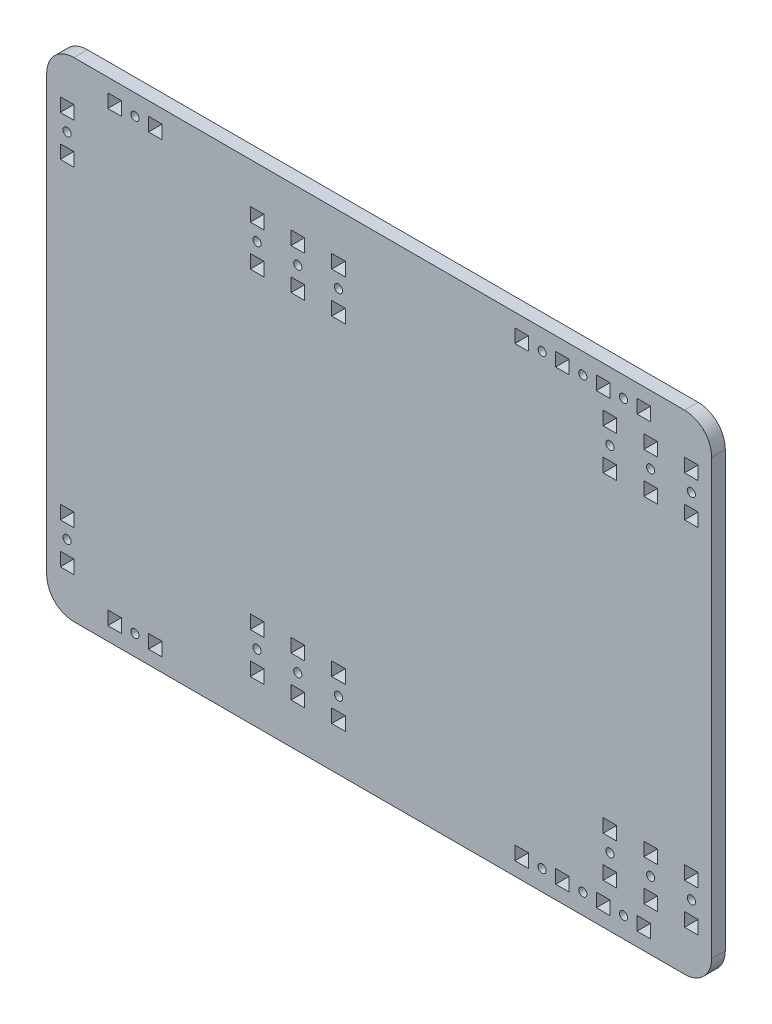
SolidWorks part; units mm, degrees
ref_plane "Front Plane" through (0, 0, 0) normal (0, 0, 1) x (1, 0, 0)
ref_plane "Top Plane" through (0, 0, 0) normal (0, 1, 0) x (1, 0, 0)
ref_plane "Right Plane" through (0, 0, 0) normal (1, 0, 0) x (0, 0, -1)
sketch "Sketch1" plane through (0, 0, 0) normal (0, 0, 1) x (1, 0, 0)
  line L0 (0, 0) -> (264.3375, 0) construction
  line L1 (-91.3244, 90) -> (153.676, 90)
  line L5 (23.6756, 97.7888) -> (23.6756, -107.1048) construction
  line L6 (-92.4996, 82.5) -> (92.5, 82.5) construction
  line L7 (92.5, -82.5) -> (-92.4996, -82.5) construction
  line L8 (-91.3244, 90) -> (-91.3244, -90)
  line L51 (-83.8244, 77.0051) -> (-83.8244, -67.4641) construction
  line L105 (-91.3244, -90) -> (153.676, -90)
  line L122 (153.676, 90) -> (153.676, -90)
  line L124 (-83.8244, 65) -> (153.676, 65) construction
  line L125 (-83.8244, -65) -> (153.676, -65) construction
  point P1 (0, 0)
  point P7 (13.7314, -65)
  point P12 (1.3999, -57.5347)
  point P13 (0, -65)
  point P14 (-14.2347, -65)
  point P26 (127.5, -49.75)
  line B0 (-63.8248, 82.5) -> (-53.8248, 82.5) construction
  line B1 (-63.8248, 85) -> (-68.8248, 85)
  line B2 (-63.8248, 85) -> (-63.8248, 80)
  line B3 (-63.8248, 80) -> (-68.8248, 80)
  line B4 (-68.8248, 85) -> (-68.8248, 80)
  line B5 (-53.8248, 85) -> (-48.8248, 85)
  line B6 (-53.8248, 85) -> (-53.8248, 80)
  line B7 (-53.8248, 80) -> (-48.8248, 80)
  line B8 (-48.8248, 85) -> (-48.8248, 80)
  line B9 (-58.8248, 82.5) -> (-58.8248, 89.4724) construction
  circle B10 centre (-58.8248, 82.5) radius 1.5
  line B11 (111.176, 82.5) -> (101.176, 82.5) construction
  line B12 (111.176, 85) -> (116.176, 85)
  line B13 (111.176, 85) -> (111.176, 80)
  line B14 (111.176, 80) -> (116.176, 80)
  line B15 (116.176, 85) -> (116.176, 80)
  line B16 (101.176, 85) -> (96.176, 85)
  line B17 (101.176, 85) -> (101.176, 80)
  line B18 (101.176, 80) -> (96.176, 80)
  line B19 (96.176, 85) -> (96.176, 80)
  line B20 (106.176, 82.5) -> (106.176, 89.4724) construction
  circle B21 centre (106.176, 82.5) radius 1.5
  line B22 (111.176, -82.5) -> (101.176, -82.5) construction
  line B23 (111.176, -85) -> (116.176, -85)
  line B24 (111.176, -85) -> (111.176, -80)
  line B25 (111.176, -80) -> (116.176, -80)
  line B26 (116.176, -85) -> (116.176, -80)
  line B27 (101.176, -85) -> (96.176, -85)
  line B28 (101.176, -85) -> (101.176, -80)
  line B29 (101.176, -80) -> (96.176, -80)
  line B30 (96.176, -85) -> (96.176, -80)
  line B31 (106.176, -82.5) -> (106.176, -89.4724) construction
  circle B32 centre (106.176, -82.5) radius 1.5
  line B33 (-63.8248, -82.5) -> (-53.8248, -82.5) construction
  line B34 (-63.8248, -85) -> (-68.8248, -85)
  line B35 (-63.8248, -85) -> (-63.8248, -80)
  line B36 (-63.8248, -80) -> (-68.8248, -80)
  line B37 (-68.8248, -85) -> (-68.8248, -80)
  line B38 (-53.8248, -85) -> (-48.8248, -85)
  line B39 (-53.8248, -85) -> (-53.8248, -80)
  line B40 (-53.8248, -80) -> (-48.8248, -80)
  line B41 (-48.8248, -85) -> (-48.8248, -80)
  line B42 (-58.8248, -82.5) -> (-58.8248, -89.4724) construction
  circle B43 centre (-58.8248, -82.5) radius 1.5
  line B44 (96.176, 82.5) -> (86.176, 82.5) construction
  line B45 (96.176, 85) -> (101.176, 85)
  line B46 (96.176, 85) -> (96.176, 80)
  line B47 (96.176, 80) -> (101.176, 80)
  line B48 (101.176, 85) -> (101.176, 80)
  line B49 (86.176, 85) -> (81.176, 85)
  line B50 (86.176, 85) -> (86.176, 80)
  line B51 (86.176, 80) -> (81.176, 80)
  line B52 (81.176, 85) -> (81.176, 80)
  line B53 (91.176, 82.5) -> (91.176, 89.4724) construction
  circle B54 centre (91.176, 82.5) radius 1.5
  line B55 (126.176, 82.5) -> (116.176, 82.5) construction
  line B56 (126.176, 85) -> (131.176, 85)
  line B57 (126.176, 85) -> (126.176, 80)
  line B58 (126.176, 80) -> (131.176, 80)
  line B59 (131.176, 85) -> (131.176, 80)
  line B60 (116.176, 85) -> (111.176, 85)
  line B61 (116.176, 85) -> (116.176, 80)
  line B62 (116.176, 80) -> (111.176, 80)
  line B63 (111.176, 85) -> (111.176, 80)
  line B64 (121.176, 82.5) -> (121.176, 89.4724) construction
  circle B65 centre (121.176, 82.5) radius 1.5
  line B66 (96.176, -82.5) -> (86.176, -82.5) construction
  line B67 (96.176, -85) -> (101.176, -85)
  line B68 (96.176, -85) -> (96.176, -80)
  line B69 (96.176, -80) -> (101.176, -80)
  line B70 (101.176, -85) -> (101.176, -80)
  line B71 (86.176, -85) -> (81.176, -85)
  line B72 (86.176, -85) -> (86.176, -80)
  line B73 (86.176, -80) -> (81.176, -80)
  line B74 (81.176, -85) -> (81.176, -80)
  line B75 (91.176, -82.5) -> (91.176, -89.4724) construction
  circle B76 centre (91.176, -82.5) radius 1.5
  line B77 (126.176, -82.5) -> (116.176, -82.5) construction
  line B78 (126.176, -85) -> (131.176, -85)
  line B79 (126.176, -85) -> (126.176, -80)
  line B80 (126.176, -80) -> (131.176, -80)
  line B81 (131.176, -85) -> (131.176, -80)
  line B82 (116.176, -85) -> (111.176, -85)
  line B83 (116.176, -85) -> (116.176, -80)
  line B84 (116.176, -80) -> (111.176, -80)
  line B85 (111.176, -85) -> (111.176, -80)
  line B86 (121.176, -82.5) -> (121.176, -89.4724) construction
  circle B87 centre (121.176, -82.5) radius 1.5
  line B88 (-83.8244, 70) -> (-83.8244, 60) construction
  line B89 (-86.3244, 70) -> (-86.3244, 75)
  line B90 (-86.3244, 70) -> (-81.3244, 70)
  line B91 (-81.3244, 70) -> (-81.3244, 75)
  line B92 (-86.3244, 75) -> (-81.3244, 75)
  line B93 (-86.3244, 60) -> (-86.3244, 55)
  line B94 (-86.3244, 60) -> (-81.3244, 60)
  line B95 (-81.3244, 60) -> (-81.3244, 55)
  line B96 (-86.3244, 55) -> (-81.3244, 55)
  line B97 (-83.8244, 65) -> (-90.7968, 65) construction
  circle B98 centre (-83.8244, 65) radius 1.5
  line B99 (-83.8244, -60) -> (-83.8244, -70) construction
  line B100 (-86.3244, -60) -> (-86.3244, -55)
  line B101 (-86.3244, -60) -> (-81.3244, -60)
  line B102 (-81.3244, -60) -> (-81.3244, -55)
  line B103 (-86.3244, -55) -> (-81.3244, -55)
  line B104 (-86.3244, -70) -> (-86.3244, -75)
  line B105 (-86.3244, -70) -> (-81.3244, -70)
  line B106 (-81.3244, -70) -> (-81.3244, -75)
  line B107 (-86.3244, -75) -> (-81.3244, -75)
  line B108 (-83.8244, -65) -> (-90.7968, -65) construction
  circle B109 centre (-83.8244, -65) radius 1.5
  line B110 (146.176, 70) -> (146.176, 60) construction
  line B111 (143.676, 70) -> (143.676, 75)
  line B112 (143.676, 70) -> (148.676, 70)
  line B113 (148.676, 70) -> (148.676, 75)
  line B114 (143.676, 75) -> (148.676, 75)
  line B115 (143.676, 60) -> (143.676, 55)
  line B116 (143.676, 60) -> (148.676, 60)
  line B117 (148.676, 60) -> (148.676, 55)
  line B118 (143.676, 55) -> (148.676, 55)
  line B119 (146.176, 65) -> (139.2036, 65) construction
  circle B120 centre (146.176, 65) radius 1.5
  line B121 (146.176, -60) -> (146.176, -70) construction
  line B122 (143.676, -60) -> (143.676, -55)
  line B123 (143.676, -60) -> (148.676, -60)
  line B124 (148.676, -60) -> (148.676, -55)
  line B125 (143.676, -55) -> (148.676, -55)
  line B126 (143.676, -70) -> (143.676, -75)
  line B127 (143.676, -70) -> (148.676, -70)
  line B128 (148.676, -70) -> (148.676, -75)
  line B129 (143.676, -75) -> (148.676, -75)
  line B130 (146.176, -65) -> (139.2036, -65) construction
  circle B131 centre (146.176, -65) radius 1.5
  line B132 (131.176, -60) -> (131.176, -70) construction
  line B133 (128.676, -60) -> (128.676, -55)
  line B134 (128.676, -60) -> (133.676, -60)
  line B135 (133.676, -60) -> (133.676, -55)
  line B136 (128.676, -55) -> (133.676, -55)
  line B137 (128.676, -70) -> (128.676, -75)
  line B138 (128.676, -70) -> (133.676, -70)
  line B139 (133.676, -70) -> (133.676, -75)
  line B140 (128.676, -75) -> (133.676, -75)
  line B141 (131.176, -65) -> (124.2036, -65) construction
  circle B142 centre (131.176, -65) radius 1.5
  line B143 (116.176, -60) -> (116.176, -70) construction
  line B144 (113.676, -60) -> (113.676, -55)
  line B145 (113.676, -60) -> (118.676, -60)
  line B146 (118.676, -60) -> (118.676, -55)
  line B147 (113.676, -55) -> (118.676, -55)
  line B148 (113.676, -70) -> (113.676, -75)
  line B149 (113.676, -70) -> (118.676, -70)
  line B150 (118.676, -70) -> (118.676, -75)
  line B151 (113.676, -75) -> (118.676, -75)
  line B152 (116.176, -65) -> (109.2036, -65) construction
  circle B153 centre (116.176, -65) radius 1.5
  line B154 (131.176, 70) -> (131.176, 60) construction
  line B155 (128.676, 70) -> (128.676, 75)
  line B156 (128.676, 70) -> (133.676, 70)
  line B157 (133.676, 70) -> (133.676, 75)
  line B158 (128.676, 75) -> (133.676, 75)
  line B159 (128.676, 60) -> (128.676, 55)
  line B160 (128.676, 60) -> (133.676, 60)
  line B161 (133.676, 60) -> (133.676, 55)
  line B162 (128.676, 55) -> (133.676, 55)
  line B163 (131.176, 65) -> (124.2036, 65) construction
  circle B164 centre (131.176, 65) radius 1.5
  line B165 (116.176, 70) -> (116.176, 60) construction
  line B166 (113.676, 70) -> (113.676, 75)
  line B167 (113.676, 70) -> (118.676, 70)
  line B168 (118.676, 70) -> (118.676, 75)
  line B169 (113.676, 75) -> (118.676, 75)
  line B170 (113.676, 60) -> (113.676, 55)
  line B171 (113.676, 60) -> (118.676, 60)
  line B172 (118.676, 60) -> (118.676, 55)
  line B173 (113.676, 55) -> (118.676, 55)
  line B174 (116.176, 65) -> (109.2036, 65) construction
  circle B175 centre (116.176, 65) radius 1.5
  line B176 (16.1756, -60) -> (16.1756, -70) construction
  line B177 (13.6756, -60) -> (13.6756, -55)
  line B178 (13.6756, -60) -> (18.6756, -60)
  line B179 (18.6756, -60) -> (18.6756, -55)
  line B180 (13.6756, -55) -> (18.6756, -55)
  line B181 (13.6756, -70) -> (13.6756, -75)
  line B182 (13.6756, -70) -> (18.6756, -70)
  line B183 (18.6756, -70) -> (18.6756, -75)
  line B184 (13.6756, -75) -> (18.6756, -75)
  line B185 (16.1756, -65) -> (9.2032, -65) construction
  circle B186 centre (16.1756, -65) radius 1.5
  line B187 (1.1756, -60) -> (1.1756, -70) construction
  line B188 (-1.3244, -60) -> (-1.3244, -55)
  line B189 (-1.3244, -60) -> (3.6756, -60)
  line B190 (3.6756, -60) -> (3.6756, -55)
  line B191 (-1.3244, -55) -> (3.6756, -55)
  line B192 (-1.3244, -70) -> (-1.3244, -75)
  line B193 (-1.3244, -70) -> (3.6756, -70)
  line B194 (3.6756, -70) -> (3.6756, -75)
  line B195 (-1.3244, -75) -> (3.6756, -75)
  line B196 (1.1756, -65) -> (-5.7968, -65) construction
  circle B197 centre (1.1756, -65) radius 1.5
  line B198 (-13.8244, -60) -> (-13.8244, -70) construction
  line B199 (-16.3244, -60) -> (-16.3244, -55)
  line B200 (-16.3244, -60) -> (-11.3244, -60)
  line B201 (-11.3244, -60) -> (-11.3244, -55)
  line B202 (-16.3244, -55) -> (-11.3244, -55)
  line B203 (-16.3244, -70) -> (-16.3244, -75)
  line B204 (-16.3244, -70) -> (-11.3244, -70)
  line B205 (-11.3244, -70) -> (-11.3244, -75)
  line B206 (-16.3244, -75) -> (-11.3244, -75)
  line B207 (-13.8244, -65) -> (-20.7968, -65) construction
  circle B208 centre (-13.8244, -65) radius 1.5
  line B209 (16.1756, 60) -> (16.1756, 70) construction
  line B210 (13.6756, 60) -> (13.6756, 55)
  line B211 (13.6756, 60) -> (18.6756, 60)
  line B212 (18.6756, 60) -> (18.6756, 55)
  line B213 (13.6756, 55) -> (18.6756, 55)
  line B214 (13.6756, 70) -> (13.6756, 75)
  line B215 (13.6756, 70) -> (18.6756, 70)
  line B216 (18.6756, 70) -> (18.6756, 75)
  line B217 (13.6756, 75) -> (18.6756, 75)
  line B218 (16.1756, 65) -> (9.2032, 65) construction
  circle B219 centre (16.1756, 65) radius 1.5
  line B220 (1.1756, 60) -> (1.1756, 70) construction
  line B221 (-1.3244, 60) -> (-1.3244, 55)
  line B222 (-1.3244, 60) -> (3.6756, 60)
  line B223 (3.6756, 60) -> (3.6756, 55)
  line B224 (-1.3244, 55) -> (3.6756, 55)
  line B225 (-1.3244, 70) -> (-1.3244, 75)
  line B226 (-1.3244, 70) -> (3.6756, 70)
  line B227 (3.6756, 70) -> (3.6756, 75)
  line B228 (-1.3244, 75) -> (3.6756, 75)
  line B229 (1.1756, 65) -> (-5.7968, 65) construction
  circle B230 centre (1.1756, 65) radius 1.5
  line B231 (-13.8244, 60) -> (-13.8244, 70) construction
  line B232 (-16.3244, 60) -> (-16.3244, 55)
  line B233 (-16.3244, 60) -> (-11.3244, 60)
  line B234 (-11.3244, 60) -> (-11.3244, 55)
  line B235 (-16.3244, 55) -> (-11.3244, 55)
  line B236 (-16.3244, 70) -> (-16.3244, 75)
  line B237 (-16.3244, 70) -> (-11.3244, 70)
  line B238 (-11.3244, 70) -> (-11.3244, 75)
  line B239 (-16.3244, 75) -> (-11.3244, 75)
  line B240 (-13.8244, 65) -> (-20.7968, 65) construction
  circle B241 centre (-13.8244, 65) radius 1.5
  dimension "D1" = 165
  dimension "D2" = 7.5
  dimension "D3" = 15
  dimension "D4" = 32.4996
  dimension "D5" = 32.5
  dimension "D6" = 7.5
  dimension "D7" = 15
  dimension "D9" = 115
  dimension "D10" = 23.6756
  dimension "D13" = 7.5
  dimension "D14" = 25
  dimension "D18" = 7.5
  dimension "D19" = 15
  dimension "D20" = 15
sketch_block_instance "Trou M3 plots 5mm-1"
sketch_block "Trou M3 plots 5mm" parameters "D2"=3, "D1"=5, "D3"=5, "D4"=10
sketch_block_instance "Trou M3 plots 5mm-3"
sketch_block_instance "Trou M3 plots 5mm-4"
sketch_block_instance "Trou M3 plots 5mm-5"
sketch_block_instance "Trou M3 plots 5mm-15"
sketch_block_instance "Trou M3 plots 5mm-16"
sketch_block_instance "Trou M3 plots 5mm-18"
sketch_block_instance "Trou M3 plots 5mm-19"
sketch_block_instance "Trou M3 plots 5mm-20"
sketch_block_instance "Trou M3 plots 5mm-21"
sketch_block_instance "Trou M3 plots 5mm-22"
sketch_block_instance "Trou M3 plots 5mm-23"
sketch_block_instance "Trou M3 plots 5mm-24"
sketch_block_instance "Trou M3 plots 5mm-25"
sketch_block_instance "Trou M3 plots 5mm-26"
sketch_block_instance "Trou M3 plots 5mm-27"
sketch_block_instance "Trou M3 plots 5mm-28"
sketch_block_instance "Trou M3 plots 5mm-29"
sketch_block_instance "Trou M3 plots 5mm-30"
sketch_block_instance "Trou M3 plots 5mm-34"
sketch_block_instance "Trou M3 plots 5mm-35"
sketch_block_instance "Trou M3 plots 5mm-36"
extrude "Boss-Extrude1" add sketch "Sketch1" along normal blind 5 contours L122 L1 L8 L105 B87 B81 B78 B79 B80 B76 B56 B59 B58 B57 B54 B52 B49 B50 B51 region at (30.7392, 0, 0)
fillet "Fillet1" radius 10 4 edges at (153.676, 90, 2.5) (153.676, -90, 2.5) (-91.3244, -90, 2.5) (-91.3244, 90, 2.5)
